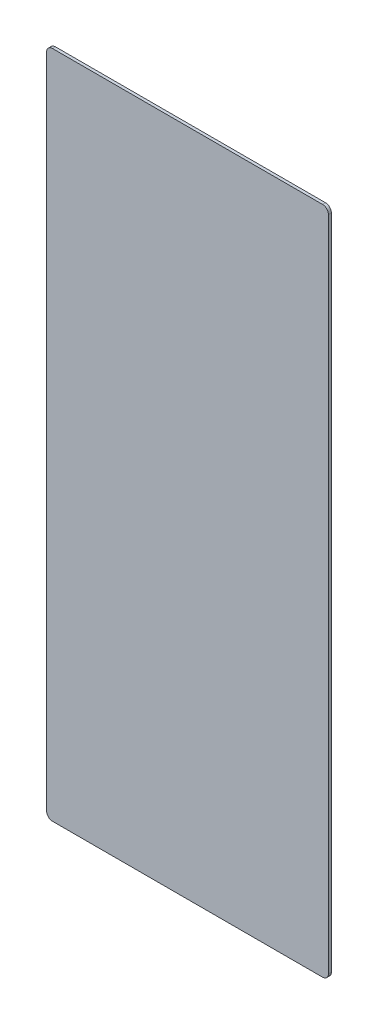
SolidWorks part; units mm, degrees
material "ABS PC"
ref_plane "Front Plane" through (0, 0, 0) normal (0, 0, 1) x (1, 0, 0)
ref_plane "Top Plane" through (0, 0, 0) normal (0, 1, 0) x (1, 0, 0)
ref_plane "Right Plane" through (0, 0, 0) normal (1, 0, 0) x (0, 0, -1)
sketch "Sketch1" plane through (0, 0, 0) normal (0, 1, 0) x (1, 0, 0)
  line L0 (-173.835, 387.1778) -> (-143.6903, 387.1778) construction
  line L1 (-58.7784, -235.1222) -> (99.215, -235.1222)
  line L2 (-65.0319, -229.8748) -> (-168.9704, 359.5894)
  line L3 (-143.6903, 387.1778) -> (99.215, 387.1778)
  line L4 (105.565, -228.7722) -> (105.565, 380.8278)
  line L5 (-64.1067, -235.1222) -> (105.565, 387.1778) construction
  line L6 (-173.835, 387.1778) -> (105.565, -235.1222) construction
  line L7 (-168.9704, 359.5894) -> (-173.835, 387.1778) construction
  line L8 (-143.6903, 387.1778) -> (-168.9704, 359.5894)
  line L9 (-173.835, 387.1778) -> (-173.835, -235.1222) construction
  line L10 (-173.835, -235.1222) -> (-58.7784, -235.1222) construction
  arc A1 (105.565, -228.7722) -> (99.215, -235.1222) centre (99.215, -228.7722) cw
  arc A2 (105.565, 380.8278) -> (99.215, 387.1778) centre (99.215, 380.8278) ccw
  arc A4 (-58.7784, -235.1222) -> (-65.0319, -229.8748) centre (-58.7784, -228.7722) cw
  point P0 (0, 0)
  dimension "D3" = 22.225
  dimension "D5" = 6.35
  dimension "D1" = 622.3
  dimension "D2" = 279.4
  dimension "D4" = 10
  dimension "D6" = 127.5
extrude "Stock to Size" [suppressed] add sketch "Sketch1" along normal blind 3.175
sketch "Sketch3" plane through (0, 0, 0) normal (0, 0, 1) x (1, 0, 0)
  line L1 (-146.05, -361.95) -> (146.05, -361.95)
  line L2 (-152.4, -355.6) -> (-152.4, 355.6)
  line L3 (-146.05, 361.95) -> (146.05, 361.95)
  line L4 (152.4, -355.6) -> (152.4, 355.6)
  line L5 (-152.4, -361.95) -> (152.4, 361.95) construction
  line L6 (-152.4, 361.95) -> (152.4, -361.95) construction
  arc A1 (152.4, -355.6) -> (146.05, -361.95) centre (146.05, -355.6) cw
  arc A2 (152.4, 355.6) -> (146.05, 361.95) centre (146.05, 355.6) ccw
  arc A4 (-146.05, -361.95) -> (-152.4, -355.6) centre (-146.05, -355.6) cw
  arc A5 (-152.4, 355.6) -> (-146.05, 361.95) centre (-146.05, 355.6) cw
  point P0 (0, 0)
  dimension "D5" = 6.35
  dimension "D1" = 723.9
  dimension "D2" = 304.8
  dimension "D4" = 90
extrude "Front Stock" add sketch "Sketch3" along normal blind 3.175
sketch "Sketch2" [suppressed] plane through (0, 3.175, 0) normal (0, 1, 0) x (1, 0, 0)
  line L2 (-193.1337, 345.5622) -> (-89.1952, -243.9021) construction
  line L3 (-82.9417, -249.1494) -> (125.8517, -249.1494) construction
  circle A0 centre (-45.6437, -198.3494) radius 2.286
  dimension "D1" = 4.572
  dimension "D2" = 50.8
  dimension "D3" = 50.8
extrude "Mounting Hole" [suppressed] cut sketch "Sketch2" against normal through all
